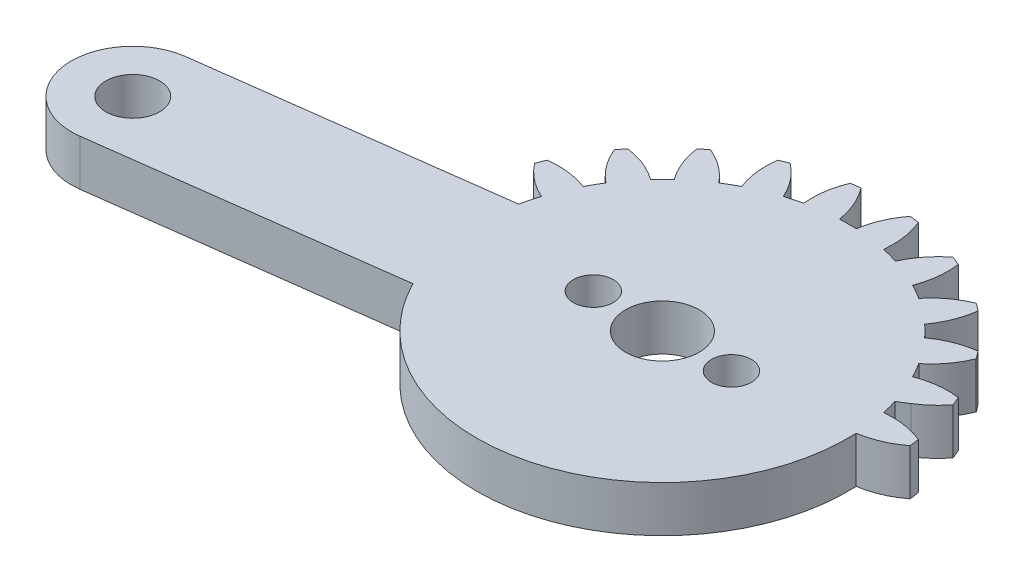
SolidWorks part; units mm, degrees
ref_plane "Front Plane" through (0, 0, 0) normal (0, 0, 1) x (1, 0, 0)
ref_plane "Top Plane" through (0, 0, 0) normal (0, 1, 0) x (1, 0, 0)
ref_plane "Right Plane" through (0, 0, 0) normal (1, 0, 0) x (0, 0, -1)
sketch "Sketch1" plane through (0, 0, 0) normal (0, 1, 0) x (1, 0, 0)
  line L0 (20.6437, 4) -> (2.0816, 4)
  line L1 (2.0816, -4) -> (20.6437, -4)
  arc A0 (2.0816, 4) -> (3.5217, 5.3071) centre (-0.7683, 8.5867) ccw
  arc A1 (3.5217, 5.3071) -> (3.2829, 5.8838) centre (-10.1063, 0) ccw
  arc A2 (3.2829, 5.8838) -> (0.6271, 5.5703) centre (2.5684, 0.5313) ccw
  arc A3 (0.6271, 5.5703) -> (0.0844, 6.5103) centre (-10.1063, 0) ccw
  arc A4 (0.0844, 6.5103) -> (1.6838, 8.6535) centre (-3.3089, 10.711) ccw
  arc A5 (1.6838, 8.6535) -> (1.3038, 9.1487) centre (-10.1063, 0) ccw
  arc A6 (1.3038, 9.1487) -> (-1.1803, 8.1585) centre (1.999, 3.7936) ccw
  arc A7 (-1.1803, 8.1585) -> (-1.9479, 8.926) centre (-10.1063, 0) ccw
  arc A8 (-1.9479, 8.926) -> (-0.9576, 11.4102) centre (-6.3127, 12.1053) ccw
  arc A9 (-0.9576, 11.4102) -> (-1.4528, 11.7901) centre (-10.1063, 0) ccw
  arc A10 (-1.4528, 11.7901) -> (-3.596, 10.1907) centre (0.6046, 6.7975) ccw
  arc A11 (-3.596, 10.1907) -> (-4.5361, 10.7334) centre (-10.1063, 0) ccw
  arc A12 (-4.5361, 10.7334) -> (-4.2225, 13.3892) centre (-9.5751, 12.6747) ccw
  arc A13 (-4.2225, 13.3892) -> (-4.7992, 13.6281) centre (-10.1063, 0) ccw
  arc A14 (-4.7992, 13.6281) -> (-6.4554, 11.5285) centre (-1.5196, 9.3381) ccw
  arc A15 (-6.4554, 11.5285) -> (-7.5039, 11.8094) centre (-10.1063, 0) ccw
  arc A16 (-7.5039, 11.8094) -> (-7.8884, 14.4558) centre (-12.8736, 12.3803) ccw
  arc A17 (-7.8884, 14.4558) -> (-8.5072, 14.5373) centre (-10.1063, 0) ccw
  arc A18 (-8.5072, 14.5373) -> (-9.5636, 12.0806) centre (-4.2291, 11.2423) ccw
  arc A19 (-9.5636, 12.0806) -> (-10.6491, 12.0806) centre (-10.1063, 0) ccw
  arc A20 (-10.6491, 12.0806) -> (-11.7054, 14.5373) centre (-15.9836, 11.2423) ccw
  arc A21 (-11.7054, 14.5373) -> (-12.3243, 14.4558) centre (-10.1063, 0) ccw
  arc A22 (-12.3243, 14.4558) -> (-12.7088, 11.8094) centre (-7.3391, 12.3803) ccw
  arc A23 (-12.7088, 11.8094) -> (-13.7573, 11.5285) centre (-10.1063, 0) ccw
  arc A24 (-13.7573, 11.5285) -> (-15.4135, 13.6281) centre (-18.6931, 9.3381) ccw
  arc A25 (-15.4135, 13.6281) -> (-15.9901, 13.3892) centre (-10.1063, 0) ccw
  arc A26 (-15.9901, 13.3892) -> (-15.6766, 10.7334) centre (-10.6376, 12.6747) ccw
  arc A27 (-15.6766, 10.7334) -> (-16.6166, 10.1907) centre (-10.1063, 0) ccw
  arc A28 (-16.6166, 10.1907) -> (-18.7599, 11.7901) centre (-20.8173, 6.7975) ccw
  arc A29 (-18.7599, 11.7901) -> (-19.255, 11.4102) centre (-10.1063, 0) ccw
  arc A30 (-19.255, 11.4102) -> (-18.2648, 8.926) centre (-13.9, 12.1053) ccw
  arc A31 (-18.2648, 8.926) -> (-19.0324, 8.1585) centre (-10.1063, 0) ccw
  arc A32 (-19.0324, 8.1585) -> (-21.5165, 9.1487) centre (-22.2117, 3.7936) ccw
  arc A33 (-21.5165, 9.1487) -> (-21.8965, 8.6535) centre (-10.1063, 0) ccw
  arc A34 (-21.8965, 8.6535) -> (-20.2971, 6.5103) centre (-16.9038, 10.711) ccw
  arc A35 (-20.2971, 6.5103) -> (-20.8398, 5.5703) centre (-10.1063, 0) ccw
  arc A36 (-20.8398, 5.5703) -> (-23.4956, 5.8838) centre (-22.7811, 0.5313) ccw
  arc A37 (-23.4956, 5.8838) -> (-23.7344, 5.3071) centre (-10.1063, 0) ccw
  arc A38 (-23.7344, 5.3071) -> (-21.6348, 3.6509) centre (-19.4444, 8.5867) ccw
  arc A39 (-21.6348, 3.6509) -> (-21.9157, 2.6025) centre (-10.1063, 0) ccw
  arc A40 (-21.9157, 2.6025) -> (-24.5622, 2.2179) centre (-22.4867, -2.7673) ccw
  arc A41 (-24.5622, 2.2179) -> (-24.6437, 1.5991) centre (-10.1063, 0) ccw
  arc A42 (-24.6437, 1.5991) -> (-22.1869, 0.5427) centre (-21.3486, 5.8773) ccw
  arc A43 (-22.1869, 0.5427) -> (-22.1869, -0.5427) centre (-10.1063, 0) ccw
  arc A44 (-22.1869, -0.5427) -> (-24.6437, -1.5991) centre (-21.3486, -5.8773) ccw
  arc A45 (-24.6437, -1.5991) -> (-24.5622, -2.2179) centre (-10.1063, 0) ccw
  arc A46 (-24.5622, -2.2179) -> (-21.9157, -2.6025) centre (-22.4867, 2.7673) ccw
  arc A47 (-21.9157, -2.6025) -> (-21.6348, -3.6509) centre (-10.1063, 0) ccw
  arc A48 (-21.6348, -3.6509) -> (-23.7344, -5.3071) centre (-19.4444, -8.5867) ccw
  arc A49 (-23.7344, -5.3071) -> (-23.4956, -5.8838) centre (-10.1063, 0) ccw
  arc A50 (-23.4956, -5.8838) -> (-20.8398, -5.5703) centre (-22.7811, -0.5313) ccw
  arc A51 (-20.8398, -5.5703) -> (-20.2971, -6.5103) centre (-10.1063, 0) ccw
  arc A52 (-20.2971, -6.5103) -> (-21.8965, -8.6535) centre (-16.9038, -10.711) ccw
  arc A53 (-21.8965, -8.6535) -> (-21.5165, -9.1487) centre (-10.1063, 0) ccw
  arc A54 (-21.5165, -9.1487) -> (-19.0324, -8.1585) centre (-22.2117, -3.7936) ccw
  arc A55 (-19.0324, -8.1585) -> (-18.2648, -8.926) centre (-10.1063, 0) ccw
  arc A56 (-18.2648, -8.926) -> (-19.255, -11.4102) centre (-13.9, -12.1053) ccw
  arc A57 (-19.255, -11.4102) -> (-18.7599, -11.7901) centre (-10.1063, 0) ccw
  arc A58 (-18.7599, -11.7901) -> (-16.6166, -10.1907) centre (-20.8173, -6.7975) ccw
  arc A59 (-16.6166, -10.1907) -> (-15.6766, -10.7334) centre (-10.1063, 0) ccw
  arc A60 (-15.6766, -10.7334) -> (-15.9901, -13.3892) centre (-10.6376, -12.6747) ccw
  arc A61 (-15.9901, -13.3892) -> (-15.4135, -13.6281) centre (-10.1063, 0) ccw
  arc A62 (-15.4135, -13.6281) -> (-13.7573, -11.5285) centre (-18.6931, -9.3381) ccw
  arc A63 (-13.7573, -11.5285) -> (-12.7088, -11.8094) centre (-10.1063, 0) ccw
  arc A64 (-12.7088, -11.8094) -> (-12.3243, -14.4558) centre (-7.3391, -12.3803) ccw
  arc A65 (-12.3243, -14.4558) -> (-11.7054, -14.5373) centre (-10.1063, 0) ccw
  arc A66 (-11.7054, -14.5373) -> (-10.6491, -12.0806) centre (-15.9836, -11.2423) ccw
  arc A67 (-10.6491, -12.0806) -> (-9.5636, -12.0806) centre (-10.1063, 0) ccw
  arc A68 (-9.5636, -12.0806) -> (-8.5072, -14.5373) centre (-4.2291, -11.2423) ccw
  arc A69 (-8.5072, -14.5373) -> (-7.8884, -14.4558) centre (-10.1063, 0) ccw
  arc A70 (-7.8884, -14.4558) -> (-7.5039, -11.8094) centre (-12.8736, -12.3803) ccw
  arc A71 (-7.5039, -11.8094) -> (-6.4554, -11.5285) centre (-10.1063, 0) ccw
  arc A72 (-6.4554, -11.5285) -> (-4.7992, -13.6281) centre (-1.5196, -9.3381) ccw
  arc A73 (-4.7992, -13.6281) -> (-4.2225, -13.3892) centre (-10.1063, 0) ccw
  arc A74 (-4.2225, -13.3892) -> (-4.5361, -10.7334) centre (-9.5751, -12.6747) ccw
  arc A75 (-4.5361, -10.7334) -> (-3.596, -10.1907) centre (-10.1063, 0) ccw
  arc A76 (-3.596, -10.1907) -> (-1.4528, -11.7901) centre (0.6046, -6.7975) ccw
  arc A77 (-1.4528, -11.7901) -> (-0.9576, -11.4102) centre (-10.1063, 0) ccw
  arc A78 (-0.9576, -11.4102) -> (-1.9479, -8.926) centre (-6.3127, -12.1053) ccw
  arc A79 (-1.9479, -8.926) -> (-1.1803, -8.1585) centre (-10.1063, 0) ccw
  arc A80 (-1.1803, -8.1585) -> (1.3038, -9.1487) centre (1.999, -3.7936) ccw
  arc A81 (1.3038, -9.1487) -> (1.6838, -8.6535) centre (-10.1063, 0) ccw
  arc A82 (1.6838, -8.6535) -> (0.0844, -6.5103) centre (-3.3089, -10.711) ccw
  arc A83 (0.0844, -6.5103) -> (0.6271, -5.5703) centre (-10.1063, 0) ccw
  arc A84 (0.6271, -5.5703) -> (3.2829, -5.8838) centre (2.5684, -0.5313) ccw
  arc A85 (3.2829, -5.8838) -> (3.5217, -5.3071) centre (-10.1063, 0) ccw
  arc A86 (3.5217, -5.3071) -> (2.0816, -4) centre (-0.7683, -8.5867) ccw
  arc A87 (20.6437, -4) -> (20.6437, 4) centre (20.6437, 0) ccw
  circle A88 centre (-10.1063, 0) radius 1.5
  circle A89 centre (20.6437, 0) radius 1.5
  dimension "D1" = 3
  dimension "D2" = 3
extrude "Boss-Extrude1" add sketch "Sketch1" along normal blind 3
sketch "Sketch3" plane through (0, 3, 0) normal (0, 1, 0) x (1, 0, 0)
  line L0 (-10.1063, 0) -> (-40.8563, 0) construction
  line L1 (-10.1063, 0) -> (-40.5933, -4.0137)
  line L2 (-10.6284, 3.9658) -> (-41.1154, -0.0479)
  line L3 (-9.5842, -3.9658) -> (-40.0712, -7.9795)
  line L4 (-10.1063, 0) -> (-4.5096, 13.5117) construction
  line L5 (-10.1063, 0) -> (-8.1974, 14.4999) construction
  circle A0 centre (-10.1063, 0) radius 1.5
  circle A1 centre (20.6437, 0) radius 1.5 construction
  circle A2 centre (20.6437, 0) radius 1.5
  circle A3 centre (-40.5933, -4.0137) radius 1.75
  circle A4 centre (-40.5933, -4.0137) radius 4
  circle A5 centre (-10.1063, 0) radius 4
  arc A6 (-4.2225, 13.3892) -> (-4.7992, 13.6281) centre (-10.1063, 0) ccw construction
  arc A7 (-7.8884, 14.4558) -> (-8.5072, 14.5373) centre (-10.1063, 0) ccw construction
  dimension "D2" = 3
  dimension "D5" = 3.5
  dimension "D6" = 8
  dimension "D7" = 8
  dimension "D1" = 30.75
  dimension "D4" = 7.5
extrude "Boss-Extrude2" add sketch "Sketch3" against normal blind 3 contours L0 A5 L2 | A5 L0 L2 A4 L1 | A4 A3 | A5 L1 A4 L3 | L0 A0 L1 A5 | A0 L0 A5 L1 region at (-13.19, 3, -2.3662) region at (-25.0786, 3, 4.0667) region at (-25.621, 3, -0.053) region at (-36.7147, 3, 3.7595)
sketch "Sketch4" plane through (0, 3, 0) normal (0, 1, 0) x (1, 0, 0)
  line L0 (20.6437, 4) -> (2.0816, 4) construction
  line L1 (2.0816, -4) -> (20.6437, -4) construction
  line L2 (20.6437, 4) -> (2.0816, 4)
  line L3 (2.0816, -4) -> (20.6437, -4)
  line L4 (2.0816, 4) -> (1.4381, 3.6001)
  line L5 (-21.6245, -5.5509) -> (-20.8986, -5.4553)
  line L6 (-10.1063, 0) -> (0.0844, 6.5103) construction
  line L7 (-10.1063, 0) -> (1.9742, 0.5427) construction
  line L8 (-24.5755, 2.1296) -> (-41.1154, -0.0479)
  line L9 (-40.0712, -7.9795) -> (-23.5312, -5.8019)
  line L10 (2.0816, -4) -> (20.6437, -4)
  line L11 (20.6437, 4) -> (2.0816, 4)
  line L12 (-21.9429, 2.4762) -> (-41.1154, -0.0479)
  line L13 (-40.0712, -7.9795) -> (-21.6245, -5.5509)
  line L14 (2.0816, -4) -> (20.6437, -4)
  line L15 (20.6437, 4) -> (2.0816, 4)
  circle A0 centre (-10.1063, 0) radius 12.0927
  arc A1 (3.2829, 5.8838) -> (0.6271, 5.5703) centre (2.5684, 0.5313) ccw construction
  arc A2 (3.5217, 5.3071) -> (3.2829, 5.8838) centre (-10.1063, 0) ccw construction
  arc A3 (2.0816, 4) -> (3.5217, 5.3071) centre (-0.7683, 8.5867) ccw construction
  arc A4 (20.6437, -4) -> (20.6437, 4) centre (20.6437, 0) ccw construction
  arc A5 (3.5217, -5.3071) -> (2.0816, -4) centre (-0.7683, -8.5867) ccw construction
  arc A6 (3.2829, -5.8838) -> (3.5217, -5.3071) centre (-10.1063, 0) ccw construction
  arc A7 (0.6271, -5.5703) -> (3.2829, -5.8838) centre (2.5684, -0.5313) ccw construction
  arc A8 (3.2829, 5.8838) -> (0.6271, 5.5703) centre (2.5684, 0.5313) ccw
  arc A9 (3.5217, 5.3071) -> (3.2829, 5.8838) centre (-10.1063, 0) ccw
  arc A10 (2.0816, 4) -> (3.5217, 5.3071) centre (-0.7683, 8.5867) ccw
  arc A11 (20.6437, -4) -> (20.6437, 4) centre (20.6437, 0) ccw
  arc A12 (3.5217, -5.3071) -> (2.0816, -4) centre (-0.7683, -8.5867) ccw
  arc A13 (3.2829, -5.8838) -> (3.5217, -5.3071) centre (-10.1063, 0) ccw
  arc A14 (0.6271, -5.5703) -> (3.2829, -5.8838) centre (2.5684, -0.5313) ccw
  arc A15 (1.9742, 0.5427) -> (4.431, 1.5991) centre (1.1359, 5.8773) ccw
  arc A16 (4.3495, 2.2179) -> (1.7031, 2.6025) centre (2.274, -2.7673) ccw
  arc A17 (4.431, 1.5991) -> (4.3495, 2.2179) centre (-10.1063, 0) ccw
  arc A95 (-21.6348, 3.6509) -> (-21.9157, 2.6025) centre (-10.1063, 0) ccw
  arc A96 (-41.1154, -0.0479) -> (-40.0712, -7.9795) centre (-40.5933, -4.0137) ccw
  arc A97 (-20.2971, -6.5103) -> (-21.8965, -8.6535) centre (-16.9038, -10.711) ccw
  arc A98 (-21.8965, -8.6535) -> (-21.5165, -9.1487) centre (-10.1063, 0) ccw
  arc A99 (-21.5165, -9.1487) -> (-19.0324, -8.1585) centre (-22.2117, -3.7936) ccw
  arc A100 (-19.0324, -8.1585) -> (-18.2648, -8.926) centre (-10.1063, 0) ccw
  arc A101 (-18.2648, -8.926) -> (-19.255, -11.4102) centre (-13.9, -12.1053) ccw
  arc A102 (-19.255, -11.4102) -> (-18.7599, -11.7901) centre (-10.1063, 0) ccw
  arc A103 (-18.7599, -11.7901) -> (-16.6166, -10.1907) centre (-20.8173, -6.7975) ccw
  arc A104 (-16.6166, -10.1907) -> (-15.6766, -10.7334) centre (-10.1063, 0) ccw
  arc A105 (-15.6766, -10.7334) -> (-15.9901, -13.3892) centre (-10.6376, -12.6747) ccw
  arc A106 (-15.9901, -13.3892) -> (-15.4135, -13.6281) centre (-10.1063, 0) ccw
  arc A107 (-15.4135, -13.6281) -> (-13.7573, -11.5285) centre (-18.6931, -9.3381) ccw
  arc A108 (-13.7573, -11.5285) -> (-12.7088, -11.8094) centre (-10.1063, 0) ccw
  arc A109 (-12.7088, -11.8094) -> (-12.3243, -14.4558) centre (-7.3391, -12.3803) ccw
  arc A110 (-12.3243, -14.4558) -> (-11.7054, -14.5373) centre (-10.1063, 0) ccw
  arc A111 (-11.7054, -14.5373) -> (-10.6491, -12.0806) centre (-15.9836, -11.2423) ccw
  arc A112 (-10.6491, -12.0806) -> (-9.5636, -12.0806) centre (-10.1063, 0) ccw
  arc A113 (-9.5636, -12.0806) -> (-8.5072, -14.5373) centre (-4.2291, -11.2423) ccw
  arc A114 (-8.5072, -14.5373) -> (-7.8884, -14.4558) centre (-10.1063, 0) ccw
  arc A115 (-7.8884, -14.4558) -> (-7.5039, -11.8094) centre (-12.8736, -12.3803) ccw
  arc A116 (-7.5039, -11.8094) -> (-6.4554, -11.5285) centre (-10.1063, 0) ccw
  arc A117 (-6.4554, -11.5285) -> (-4.7992, -13.6281) centre (-1.5196, -9.3381) ccw
  arc A118 (-4.7992, -13.6281) -> (-4.2225, -13.3892) centre (-10.1063, 0) ccw
  arc A119 (-4.2225, -13.3892) -> (-4.5361, -10.7334) centre (-9.5751, -12.6747) ccw
  arc A120 (-4.5361, -10.7334) -> (-3.596, -10.1907) centre (-10.1063, 0) ccw
  arc A121 (-3.596, -10.1907) -> (-1.4528, -11.7901) centre (0.6046, -6.7975) ccw
  arc A122 (-1.4528, -11.7901) -> (-0.9576, -11.4102) centre (-10.1063, 0) ccw
  arc A123 (-0.9576, -11.4102) -> (-1.9479, -8.926) centre (-6.3127, -12.1053) ccw
  arc A124 (-1.9479, -8.926) -> (-1.1803, -8.1585) centre (-10.1063, 0) ccw
  arc A125 (-1.1803, -8.1585) -> (1.3038, -9.1487) centre (1.999, -3.7936) ccw
  arc A126 (1.3038, -9.1487) -> (1.6838, -8.6535) centre (-10.1063, 0) ccw
  arc A127 (1.6838, -8.6535) -> (0.0844, -6.5103) centre (-3.3089, -10.711) ccw
  arc A128 (0.0844, -6.5103) -> (0.6271, -5.5703) centre (-10.1063, 0) ccw
  arc A129 (0.6271, -5.5703) -> (3.2829, -5.8838) centre (2.5684, -0.5313) ccw
  arc A130 (3.2829, -5.8838) -> (3.5217, -5.3071) centre (-10.1063, 0) ccw
  arc A131 (3.5217, -5.3071) -> (2.0816, -4) centre (-0.7683, -8.5867) ccw
  arc A132 (20.6437, -4) -> (20.6437, 4) centre (20.6437, 0) ccw
  arc A133 (2.0816, 4) -> (3.5217, 5.3071) centre (-0.7683, 8.5867) ccw
  arc A134 (3.5217, 5.3071) -> (3.2829, 5.8838) centre (-10.1063, 0) ccw
  arc A135 (3.2829, 5.8838) -> (0.6271, 5.5703) centre (2.5684, 0.5313) ccw
  arc A136 (0.6271, 5.5703) -> (0.0844, 6.5103) centre (-10.1063, 0) ccw
  arc A137 (0.0844, 6.5103) -> (1.6838, 8.6535) centre (-3.3089, 10.711) ccw
  arc A138 (1.6838, 8.6535) -> (1.3038, 9.1487) centre (-10.1063, 0) ccw
  arc A139 (1.3038, 9.1487) -> (-1.1803, 8.1585) centre (1.999, 3.7936) ccw
  arc A140 (-1.1803, 8.1585) -> (-1.9479, 8.926) centre (-10.1063, 0) ccw
  arc A141 (-1.9479, 8.926) -> (-0.9576, 11.4102) centre (-6.3127, 12.1053) ccw
  arc A142 (-0.9576, 11.4102) -> (-1.4528, 11.7901) centre (-10.1063, 0) ccw
  arc A143 (-1.4528, 11.7901) -> (-3.596, 10.1907) centre (0.6046, 6.7975) ccw
  arc A144 (-3.596, 10.1907) -> (-4.5361, 10.7334) centre (-10.1063, 0) ccw
  arc A145 (-4.5361, 10.7334) -> (-4.2225, 13.3892) centre (-9.5751, 12.6747) ccw
  arc A146 (-4.2225, 13.3892) -> (-4.7992, 13.6281) centre (-10.1063, 0) ccw
  arc A147 (-4.7992, 13.6281) -> (-6.4554, 11.5285) centre (-1.5196, 9.3381) ccw
  arc A148 (-6.4554, 11.5285) -> (-7.5039, 11.8094) centre (-10.1063, 0) ccw
  arc A149 (-7.5039, 11.8094) -> (-7.8884, 14.4558) centre (-12.8736, 12.3803) ccw
  arc A150 (-7.8884, 14.4558) -> (-8.5072, 14.5373) centre (-10.1063, 0) ccw
  arc A151 (-8.5072, 14.5373) -> (-9.5636, 12.0806) centre (-4.2291, 11.2423) ccw
  arc A152 (-9.5636, 12.0806) -> (-10.6491, 12.0806) centre (-10.1063, 0) ccw
  arc A153 (-10.6491, 12.0806) -> (-11.7054, 14.5373) centre (-15.9836, 11.2423) ccw
  arc A154 (-11.7054, 14.5373) -> (-12.3243, 14.4558) centre (-10.1063, 0) ccw
  arc A155 (-12.3243, 14.4558) -> (-12.7088, 11.8094) centre (-7.3391, 12.3803) ccw
  arc A156 (-12.7088, 11.8094) -> (-13.7573, 11.5285) centre (-10.1063, 0) ccw
  arc A157 (-13.7573, 11.5285) -> (-15.4135, 13.6281) centre (-18.6931, 9.3381) ccw
  arc A158 (-15.4135, 13.6281) -> (-15.9901, 13.3892) centre (-10.1063, 0) ccw
  arc A159 (-15.9901, 13.3892) -> (-15.6766, 10.7334) centre (-10.6376, 12.6747) ccw
  arc A160 (-15.6766, 10.7334) -> (-16.6166, 10.1907) centre (-10.1063, 0) ccw
  arc A161 (-16.6166, 10.1907) -> (-18.7599, 11.7901) centre (-20.8173, 6.7975) ccw
  arc A162 (-18.7599, 11.7901) -> (-19.255, 11.4102) centre (-10.1063, 0) ccw
  arc A163 (-19.255, 11.4102) -> (-18.2648, 8.926) centre (-13.9, 12.1053) ccw
  arc A164 (-18.2648, 8.926) -> (-19.0324, 8.1585) centre (-10.1063, 0) ccw
  arc A165 (-19.0324, 8.1585) -> (-21.5165, 9.1487) centre (-22.2117, 3.7936) ccw
  arc A166 (-21.5165, 9.1487) -> (-21.8965, 8.6535) centre (-10.1063, 0) ccw
  arc A167 (-21.8965, 8.6535) -> (-20.2971, 6.5103) centre (-16.9038, 10.711) ccw
  arc A168 (-20.2971, 6.5103) -> (-20.8398, 5.5703) centre (-10.1063, 0) ccw
  arc A169 (-20.8398, 5.5703) -> (-23.4956, 5.8838) centre (-22.7811, 0.5313) ccw
  arc A170 (-23.4956, 5.8838) -> (-23.7344, 5.3071) centre (-10.1063, 0) ccw
  arc A171 (-23.7344, 5.3071) -> (-21.6348, 3.6509) centre (-19.4444, 8.5867) ccw
  arc A172 (-21.6348, 3.6509) -> (-21.9157, 2.6025) centre (-10.1063, 0) ccw
  arc A175 (-23.4956, -5.8838) -> (-20.8398, -5.5703) centre (-22.7811, -0.5313) ccw
  arc A176 (-41.1154, -0.0479) -> (-40.0712, -7.9795) centre (-40.5933, -4.0137) ccw
  arc A177 (-20.2971, -6.5103) -> (-21.8965, -8.6535) centre (-16.9038, -10.711) ccw
  arc A178 (-21.8965, -8.6535) -> (-21.5165, -9.1487) centre (-10.1063, 0) ccw
  arc A179 (-21.5165, -9.1487) -> (-19.0324, -8.1585) centre (-22.2117, -3.7936) ccw
  arc A180 (-19.0324, -8.1585) -> (-18.2648, -8.926) centre (-10.1063, 0) ccw
  arc A181 (-18.2648, -8.926) -> (-19.255, -11.4102) centre (-13.9, -12.1053) ccw
  arc A182 (-19.255, -11.4102) -> (-18.7599, -11.7901) centre (-10.1063, 0) ccw
  arc A183 (-18.7599, -11.7901) -> (-16.6166, -10.1907) centre (-20.8173, -6.7975) ccw
  arc A184 (-16.6166, -10.1907) -> (-15.6766, -10.7334) centre (-10.1063, 0) ccw
  arc A185 (-15.6766, -10.7334) -> (-15.9901, -13.3892) centre (-10.6376, -12.6747) ccw
  arc A186 (-15.9901, -13.3892) -> (-15.4135, -13.6281) centre (-10.1063, 0) ccw
  arc A187 (-15.4135, -13.6281) -> (-13.7573, -11.5285) centre (-18.6931, -9.3381) ccw
  arc A188 (-13.7573, -11.5285) -> (-12.7088, -11.8094) centre (-10.1063, 0) ccw
  arc A189 (-12.7088, -11.8094) -> (-12.3243, -14.4558) centre (-7.3391, -12.3803) ccw
  arc A190 (-12.3243, -14.4558) -> (-11.7054, -14.5373) centre (-10.1063, 0) ccw
  arc A191 (-11.7054, -14.5373) -> (-10.6491, -12.0806) centre (-15.9836, -11.2423) ccw
  arc A192 (-10.6491, -12.0806) -> (-9.5636, -12.0806) centre (-10.1063, 0) ccw
  arc A193 (-9.5636, -12.0806) -> (-8.5072, -14.5373) centre (-4.2291, -11.2423) ccw
  arc A194 (-8.5072, -14.5373) -> (-7.8884, -14.4558) centre (-10.1063, 0) ccw
  arc A195 (-7.8884, -14.4558) -> (-7.5039, -11.8094) centre (-12.8736, -12.3803) ccw
  arc A196 (-7.5039, -11.8094) -> (-6.4554, -11.5285) centre (-10.1063, 0) ccw
  arc A197 (-6.4554, -11.5285) -> (-4.7992, -13.6281) centre (-1.5196, -9.3381) ccw
  arc A198 (-4.7992, -13.6281) -> (-4.2225, -13.3892) centre (-10.1063, 0) ccw
  arc A199 (-4.2225, -13.3892) -> (-4.5361, -10.7334) centre (-9.5751, -12.6747) ccw
  arc A200 (-4.5361, -10.7334) -> (-3.596, -10.1907) centre (-10.1063, 0) ccw
  arc A201 (-3.596, -10.1907) -> (-1.4528, -11.7901) centre (0.6046, -6.7975) ccw
  arc A202 (-1.4528, -11.7901) -> (-0.9576, -11.4102) centre (-10.1063, 0) ccw
  arc A203 (-0.9576, -11.4102) -> (-1.9479, -8.926) centre (-6.3127, -12.1053) ccw
  arc A204 (-1.9479, -8.926) -> (-1.1803, -8.1585) centre (-10.1063, 0) ccw
  arc A205 (-1.1803, -8.1585) -> (1.3038, -9.1487) centre (1.999, -3.7936) ccw
  arc A206 (1.3038, -9.1487) -> (1.6838, -8.6535) centre (-10.1063, 0) ccw
  arc A207 (1.6838, -8.6535) -> (0.0844, -6.5103) centre (-3.3089, -10.711) ccw
  arc A208 (0.0844, -6.5103) -> (0.6271, -5.5703) centre (-10.1063, 0) ccw
  arc A209 (0.6271, -5.5703) -> (3.2829, -5.8838) centre (2.5684, -0.5313) ccw
  arc A210 (3.2829, -5.8838) -> (3.5217, -5.3071) centre (-10.1063, 0) ccw
  arc A211 (3.5217, -5.3071) -> (2.0816, -4) centre (-0.7683, -8.5867) ccw
  arc A212 (20.6437, -4) -> (20.6437, 4) centre (20.6437, 0) ccw
  arc A213 (2.0816, 4) -> (3.5217, 5.3071) centre (-0.7683, 8.5867) ccw
  arc A214 (3.5217, 5.3071) -> (3.2829, 5.8838) centre (-10.1063, 0) ccw
  arc A215 (3.2829, 5.8838) -> (0.6271, 5.5703) centre (2.5684, 0.5313) ccw
  arc A216 (0.6271, 5.5703) -> (0.0844, 6.5103) centre (-10.1063, 0) ccw
  arc A217 (0.0844, 6.5103) -> (1.6838, 8.6535) centre (-3.3089, 10.711) ccw
  arc A218 (1.6838, 8.6535) -> (1.3038, 9.1487) centre (-10.1063, 0) ccw
  arc A219 (1.3038, 9.1487) -> (-1.1803, 8.1585) centre (1.999, 3.7936) ccw
  arc A220 (-1.1803, 8.1585) -> (-1.9479, 8.926) centre (-10.1063, 0) ccw
  arc A221 (-1.9479, 8.926) -> (-0.9576, 11.4102) centre (-6.3127, 12.1053) ccw
  arc A222 (-0.9576, 11.4102) -> (-1.4528, 11.7901) centre (-10.1063, 0) ccw
  arc A223 (-1.4528, 11.7901) -> (-3.596, 10.1907) centre (0.6046, 6.7975) ccw
  arc A224 (-3.596, 10.1907) -> (-4.5361, 10.7334) centre (-10.1063, 0) ccw
  arc A225 (-4.5361, 10.7334) -> (-4.2225, 13.3892) centre (-9.5751, 12.6747) ccw
  arc A226 (-4.2225, 13.3892) -> (-4.7992, 13.6281) centre (-10.1063, 0) ccw
  arc A227 (-4.7992, 13.6281) -> (-6.4554, 11.5285) centre (-1.5196, 9.3381) ccw
  arc A228 (-6.4554, 11.5285) -> (-7.5039, 11.8094) centre (-10.1063, 0) ccw
  arc A229 (-7.5039, 11.8094) -> (-7.8884, 14.4558) centre (-12.8736, 12.3803) ccw
  arc A230 (-7.8884, 14.4558) -> (-8.5072, 14.5373) centre (-10.1063, 0) ccw
  arc A231 (-8.5072, 14.5373) -> (-9.5636, 12.0806) centre (-4.2291, 11.2423) ccw
  arc A232 (-9.5636, 12.0806) -> (-10.6491, 12.0806) centre (-10.1063, 0) ccw
  arc A233 (-10.6491, 12.0806) -> (-11.7054, 14.5373) centre (-15.9836, 11.2423) ccw
  arc A234 (-11.7054, 14.5373) -> (-12.3243, 14.4558) centre (-10.1063, 0) ccw
  arc A235 (-12.3243, 14.4558) -> (-12.7088, 11.8094) centre (-7.3391, 12.3803) ccw
  arc A236 (-12.7088, 11.8094) -> (-13.7573, 11.5285) centre (-10.1063, 0) ccw
  arc A237 (-13.7573, 11.5285) -> (-15.4135, 13.6281) centre (-18.6931, 9.3381) ccw
  arc A238 (-15.4135, 13.6281) -> (-15.9901, 13.3892) centre (-10.1063, 0) ccw
  arc A239 (-15.9901, 13.3892) -> (-15.6766, 10.7334) centre (-10.6376, 12.6747) ccw
  arc A240 (-15.6766, 10.7334) -> (-16.6166, 10.1907) centre (-10.1063, 0) ccw
  arc A241 (-16.6166, 10.1907) -> (-18.7599, 11.7901) centre (-20.8173, 6.7975) ccw
  arc A242 (-18.7599, 11.7901) -> (-19.255, 11.4102) centre (-10.1063, 0) ccw
  arc A243 (-19.255, 11.4102) -> (-18.2648, 8.926) centre (-13.9, 12.1053) ccw
  arc A244 (-18.2648, 8.926) -> (-19.0324, 8.1585) centre (-10.1063, 0) ccw
  arc A245 (-19.0324, 8.1585) -> (-21.5165, 9.1487) centre (-22.2117, 3.7936) ccw
  arc A246 (-21.5165, 9.1487) -> (-21.8965, 8.6535) centre (-10.1063, 0) ccw
  arc A247 (-21.8965, 8.6535) -> (-20.2971, 6.5103) centre (-16.9038, 10.711) ccw
  arc A248 (-20.2971, 6.5103) -> (-20.8398, 5.5703) centre (-10.1063, 0) ccw
  arc A249 (-20.8398, 5.5703) -> (-23.4956, 5.8838) centre (-22.7811, 0.5313) ccw
  arc A250 (-23.4956, 5.8838) -> (-23.7344, 5.3071) centre (-10.1063, 0) ccw
  arc A251 (-23.7344, 5.3071) -> (-21.6348, 3.6509) centre (-19.4444, 8.5867) ccw
  arc A252 (-23.4956, -5.8838) -> (-20.8398, -5.5703) centre (-22.7811, -0.5313) ccw
  arc A253 (-20.8398, -5.5703) -> (-20.2971, -6.5103) centre (-10.1063, 0) ccw
  arc A254 (-20.8398, -5.5703) -> (-20.2971, -6.5103) centre (-10.1063, 0) ccw
  arc A255 (-23.5312, -5.8019) -> (-23.4956, -5.8838) centre (-10.1063, 0) ccw
  arc A256 (-23.5312, -5.8019) -> (-23.4956, -5.8838) centre (-10.1063, 0) ccw
  arc A257 (-21.9157, 2.6025) -> (-24.5622, 2.2179) centre (-22.4867, -2.7673) ccw
  arc A258 (-21.9157, 2.6025) -> (-24.5622, 2.2179) centre (-22.4867, -2.7673) ccw
  arc A259 (-24.5622, 2.2179) -> (-24.5755, 2.1296) centre (-10.1063, 0) ccw
  arc A260 (-24.5622, 2.2179) -> (-24.5755, 2.1296) centre (-10.1063, 0) ccw
  point P40 (-10.1063, 0)
  dimension "D2" = 24.1855
  dimension "D4" = 30
  dimension "D1" = 0
  dimension "D3" = 2
extrude "Cut-Extrude1" cut sketch "Sketch4" against normal blind 4 contours A178 A179 A0 L5 A177 | A182 A183 A0 A181 | A186 A187 A0 A185 | A190 A191 A0 A189 | A194 A195 A0 A193 | A198 A199 A0 A197 | A202 A203 A0 A201 | A206 A207 A0 A205 | A258 A260 L12 A0 | L13 A256 A252 A0 L5 | A0 A14 A13 A12 L3 A11 L2 L4 region at (12.7894, 3, 0.1545) region at (0.3325, 3, 8.01) region at (-2.0963, 3, 10.4389) region at (-5.071, 3, 12.1563) region at (-8.3889, 3, 13.0454) region at (-11.8238, 3, 13.0454) region at (-15.1417, 3, 12.1563) region at (-18.1164, 3, 10.4389) region at (-20.5452, 3, 8.01) region at (-23.2126, 3, -2.4243) region at (-22.1386, 3, 5.7339)
sketch "Sketch5" plane through (0, 3, 0) normal (0, 1, 0) x (1, 0, 0)
  circle A0 centre (-10.1063, 0) radius 2.4
  circle A1 centre (-5.6063, 0) radius 1.3
  circle A2 centre (-14.6063, 0) radius 1.3
  circle A3 centre (-10.1063, 0) radius 1.5 construction
  dimension "D1" = 4.8
  dimension "D2" = 2.6
  dimension "D3" = 2.6
  dimension "D4" = 4.5
  dimension "D5" = 9
extrude "Cut-Extrude2" cut sketch "Sketch5" against normal up to next contours A2 | A1 | A0 region at (-5.6063, 3, 0) region at (-14.6063, 3, 0)
